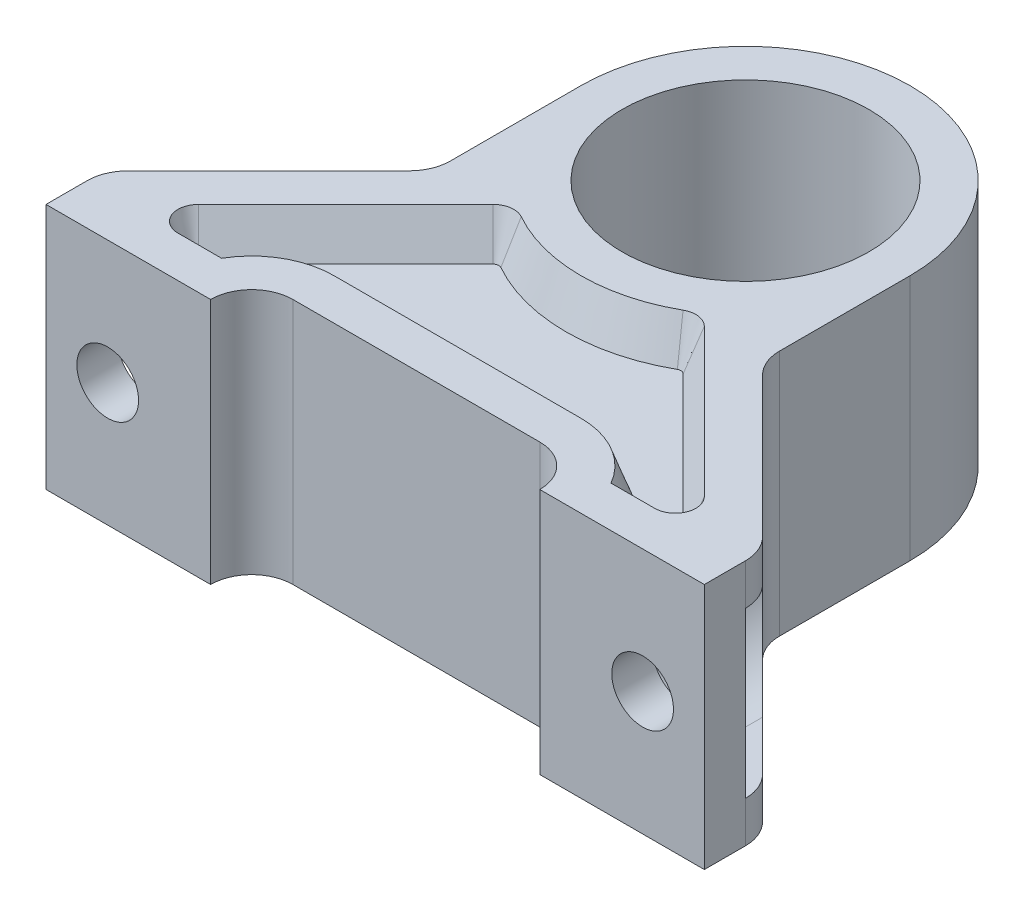
SolidWorks part; units mm, degrees
material "Cast Carbon Steel"
ref_plane "Front Plane" through (0, 0, 0) normal (0, 0, 1) x (1, 0, 0)
ref_plane "Top Plane" through (0, 0, 0) normal (0, 1, 0) x (1, 0, 0)
ref_plane "Right Plane" through (0, 0, 0) normal (1, 0, 0) x (0, 0, -1)
sketch "Sketch1" plane through (0, 0, 0) normal (0, 1, 0) x (1, 0, 0)
  line L0 (0, 0) -> (-203.2, 0)
  line L1 (-203.2, 0) -> (-203.2, 12.7)
  line L2 (-199.4803, 21.6803) -> (-156.1197, 65.0408)
  line L3 (-152.4, 74.021) -> (-152.4, 114.3)
  line L4 (-50.8, 114.3) -> (-50.8, 74.021)
  line L5 (-47.0803, 65.0408) -> (-3.7197, 21.6803)
  line L6 (0, 12.7) -> (0, 0)
  arc A0 (-152.4, 114.3) -> (-50.8, 114.3) centre (-101.6, 114.3) cw
  arc A1 (-50.8, 74.021) -> (-47.0803, 65.0408) centre (-38.1, 74.021) ccw
  arc A2 (-156.1197, 65.0408) -> (-152.4, 74.021) centre (-165.1, 74.021) ccw
  arc A3 (-3.7197, 21.6803) -> (0, 12.7) centre (-12.7, 12.7) cw
  arc A4 (-203.2, 12.7) -> (-199.4803, 21.6803) centre (-190.5, 12.7) cw
  circle A5 centre (-101.6, 114.3) radius 38.1
  point P2 (-101.6, 0)
  dimension "D3" = 12.7
  dimension "D8" = 50.8
  dimension "D9" = 76.2
  dimension "D1" = 203.2
  dimension "D2" = 114.3
  dimension "D4" = 12.7
  dimension "D5" = 12.7
  dimension "D6" = 45
  dimension "D7" = 45
extrude "Boss-Extrude1" add sketch "Sketch1" along normal blind 76.2
sketch "Sketch2" plane through (0, 76.2, 0) normal (0, 1, 0) x (1, 0, 0)
  line L0 (-139.7, 0) -> (-63.5, 0) construction
  line L1 (-203.2, 0) -> (0, 0) construction
  line L2 (-139.7, 12.7) -> (-63.5, 12.7)
  line L3 (-139.7, -12.7) -> (-63.5, -12.7)
  arc A0 (-139.7, 12.7) -> (-139.7, -12.7) centre (-139.7, 0) ccw
  arc A1 (-63.5, -12.7) -> (-63.5, 12.7) centre (-63.5, 0) ccw
  point P4 (-101.6, 0)
  dimension "D1" = 12.7
  dimension "D2" = 76.2
extrude "Cut-Extrude1" cut sketch "Sketch2" against normal through all
sketch "Sketch4" plane through (0, 0, 0) normal (0, 0, 1) x (1, 0, 0)
  line L0 (0, 63.5) -> (-19.05, 63.5)
  line L1 (0, 76.2) -> (0, 0) construction
  line L2 (-19.05, 12.7) -> (0, 12.7)
  line L3 (0, 63.5) -> (0, 12.7)
  line L4 (-203.2, 76.2) -> (-203.2, 0) construction
  arc A0 (-19.05, 63.5) -> (-19.05, 12.7) centre (-19.05, 38.1) ccw
  point P6 (-19.05, 36.2254)
  point P10 (-203.2, 38.1)
  dimension "D1" = 19.05
  dimension "D2" = 50.8
extrude "Cut-Extrude2" cut sketch "Sketch4" against normal through all from offset 12.7 offset against normal yes
sketch "Sketch5" plane through (0, 0, -12.7) normal (0, 0, -1) x (-1, 0, 0)
  circle A0 centre (19.05, 38.1) radius 9.525
  dimension "D1" = 19.05
extrude "Cut-Extrude3" cut sketch "Sketch5" against normal through all
ref_plane "Plane1" through (-101.6, 0, 0) normal (1, 0, 0) x (0, 0, -1)
mirror "Mirror1" about plane through (-101.6, 0, 0) normal (1, 0, 0) of "Cut-Extrude2", "Cut-Extrude3"
sketch "Sketch6" plane through (0, 76.2, 0) normal (0, 1, 0) x (1, 0, 0)
  line L92 (-12.7, 12.7) -> (-56.0605, 56.0605)
  line L93 (-41.503, 12.7) -> (-12.7, 12.7)
  line L94 (-139.7, 25.4) -> (-63.5, 25.4)
  line L95 (-190.5, 12.7) -> (-161.697, 12.7)
  line L96 (-147.1395, 56.0605) -> (-190.5, 12.7)
  line L97 (-23.5401, 23.5401) -> (-69.0199, 69.0199)
  line L98 (-41.503, 12.7) -> (-28.0303, 12.7)
  line L99 (-139.7, 25.4) -> (-63.5, 25.4)
  line L100 (-175.1697, 12.7) -> (-161.697, 12.7)
  line L101 (-134.1801, 69.0199) -> (-179.6599, 23.5401)
  arc A57 (-69.0199, 69.0199) -> (-76.6311, 70.0598) centre (-73.51, 64.5298) ccw
  circle A58 centre (-101.6, 114.3) radius 50.8
  arc A59 (-126.5689, 70.0598) -> (-76.6311, 70.0598) centre (-101.6, 114.3) ccw
  arc A60 (-41.503, 12.7) -> (-63.5, 25.4) centre (-63.5, 0) ccw
  arc A61 (-139.7, 25.4) -> (-161.697, 12.7) centre (-139.7, 0) ccw
  arc A62 (-41.503, 12.7) -> (-63.5, 25.4) centre (-63.5, 0) ccw
  arc A63 (-139.7, 25.4) -> (-161.697, 12.7) centre (-139.7, 0) ccw
  arc A64 (-134.1801, 69.0199) -> (-126.5689, 70.0598) centre (-129.69, 64.5298) cw
  arc A65 (-23.5401, 23.5401) -> (-28.0303, 12.7) centre (-28.0303, 19.05) cw
  arc A66 (-175.1697, 12.7) -> (-179.6599, 23.5401) centre (-175.1697, 19.05) cw
  point P0 (-72.5947, 72.5947)
  dimension "D3" = 6.35
  dimension "D4" = 6.35
  dimension "D1" = 12.7
  dimension "D2" = 12.7
extrude "Cut-Extrude4" cut sketch "Sketch6" against normal blind 12.7
chamfer "Chamfer1" distance 12.7 angle 20 12 edges at (-46.28, 63.5, -46.28) (-22.1636, 63.5, -16.62) (-34.7666, 63.5, -12.7) (-50.8, 63.5, -21.997) (-101.6, 63.5, -25.4) (-152.4, 63.5, -21.997) (-168.4334, 63.5, -12.7) (-181.0364, 63.5, -16.62) (-156.92, 63.5, -46.28) (-130.5496, 63.5, -70.8213) (-101.6, 63.5, -63.5) (-72.6504, 63.5, -70.8213) first distance on face at (-46.28, 69.85, -46.28) first distance on face at (-23.9744, 69.85, -17.37) first distance on face at (-34.7666, 69.85, -12.7) first distance on face at (-51.6507, 69.85, -20.5235) first distance on face at (-101.6, 69.85, -25.4) first distance on face at (-151.5493, 69.85, -20.5235) first distance on face at (-168.4334, 69.85, -12.7) first distance on face at (-179.2256, 69.85, -17.37) first distance on face at (-156.92, 69.85, -46.28) first distance on face at (-130.462, 69.85, -70.1806) first distance on face at (-101.6, 69.85, -66.7799) first distance on face at (-72.738, 69.85, -70.1806)
ref_plane "Plane2" through (0, 38.1, 0) normal (0, 1, 0) x (1, 0, 0)
mirror "Mirror2" about plane through (0, 38.1, 0) normal (0, 1, 0) of "Chamfer1", "Cut-Extrude4"
equation "\"A\"= 3.00in"
equation "\"B\"= 4.00in"
equation "\"D9@Sketch1\"=\"A\""
